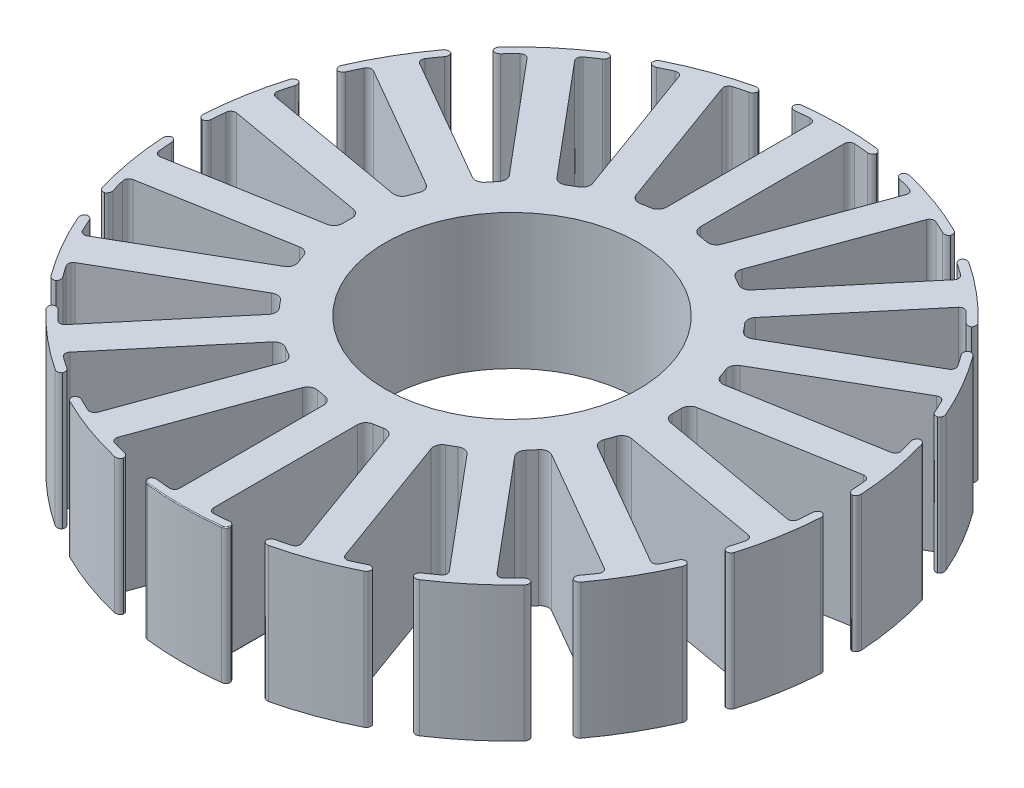
SolidWorks part; units mm, degrees
material "Ductile Iron"
ref_plane "Front Plane" through (0, 0, 0) normal (0, 0, 1) x (1, 0, 0)
ref_plane "Top Plane" through (0, 0, 0) normal (0, 1, 0) x (1, 0, 0)
ref_plane "Right Plane" through (0, 0, 0) normal (1, 0, 0) x (0, 0, -1)
sketch "Sketch1" plane through (0, 0, 0) normal (0, 1, 0) x (1, 0, 0)
  circle A1 centre (0, 0) radius 9.75
  dimension "D1" = 19.5
extrude "Boss-Extrude1" add sketch "Sketch1" along normal mid plane 8
ref_axis "Axis1" through (0, 4, 0) along (0, -1, 0)
sketch "Sketch2" plane through (0, 4, 0) normal (0, 1, 0) x (1, 0, 0)
  line L0 (0, 0) -> (0, 19.5) construction
  line L1 (-2.5, 19.3391) -> (-2.4359, 18.8432)
  line L2 (2.5, 19.3391) -> (2.4359, 18.8432)
  line L3 (-1, 18.9737) -> (-1, 9.6986)
  line L4 (1, 18.9737) -> (1, 9.6986)
  circle A0 centre (0, 0) radius 9.75 construction
  arc A1 (1, 9.6986) -> (-1, 9.6986) centre (0, 0) ccw
  arc A2 (2.5, 19.3391) -> (-2.5, 19.3391) centre (0, 0) ccw
  arc A3 (2.4359, 18.8432) -> (1, 18.9737) centre (0, 0) ccw
  arc A4 (-1, 18.9737) -> (-2.4359, 18.8432) centre (0, 0) ccw
  dimension "D1" = 19.5
  dimension "D2" = 0.5
  dimension "D3" = 2
  dimension "D4" = 5
extrude "Boss-Extrude2" add sketch "Sketch2" against normal up to surface (8 mm away) up to face at (0, -4, 9.75)
fillet "Fillet1" radius 0.3 6 edges at (-1, 0, -18.9737) (1, 0, -18.9737) (2.5, 0, -19.3391) (2.4359, 0, -18.8432) (-2.5, 0, -19.3391) (-2.4359, 0, -18.8432)
pattern_circular "CirPattern1" count 18 over 360 about axis through (0, 4, 0) along (0, -1, 0) of "Boss-Extrude2", "Fillet1"
fillet "Fillet2" radius 0.5 36 edges at (-5.4681, 0, 8.0723) (-4.2568, 0, 8.7717) (-2.3774, 0, 9.4557) (-1, 0, 9.6986) (1, 0, 9.6986) (2.3774, 0, 9.4557) (4.2568, 0, 8.7717) (5.4681, 0, 8.0723) (7.0002, 0, 6.7868) (7.8992, 0, 5.7153) (8.8992, 0, 3.9833) (9.3776, 0, 2.6689) (9.7249, 0, 0.6993) (9.7249, 0, -0.6993) (9.3776, 0, -2.6689) (8.8992, 0, -3.9833) (7.0002, 0, -6.7868) (-7.0002, 0, 6.7868) (1, 0, -9.6986) (4.2568, 0, -8.7717) (7.8992, 0, -5.7153) (5.4681, 0, -8.0723) (2.3774, 0, -9.4557) (-1, 0, -9.6986) (-4.2568, 0, -8.7717) (-2.3774, 0, -9.4557) (-7.0002, 0, -6.7868) (-5.4681, 0, -8.0723) (-8.8992, 0, -3.9833) (-7.8992, 0, -5.7153) (-9.7249, 0, -0.6993) (-9.3776, 0, -2.6689) (-9.3776, 0, 2.6689) (-9.7249, 0, 0.6993) (-8.8992, 0, 3.9833) (-7.8992, 0, 5.7153)
sketch "Sketch3" plane through (0, 4, 0) normal (0, 1, 0) x (1, 0, 0)
  circle A0 centre (0, 0) radius 7.5
  dimension "D1" = 15
extrude "Cut-Extrude1" cut sketch "Sketch3" against normal through all
fillet "Fillet3" radius 0.05 10 edges at (5.426, -4, 18.1105) (4.8436, -4, 18.3723) (1.7322, -4, 18.9209) (1.0954, -4, 18.8741) (1, -4, 14.3972) (1.1215, -4, 9.813) (1.6931, -4, 9.6019) (2.3024, -4, 9.6048) (3.9844, -4, 13.871) (0, 4, 19.5)
